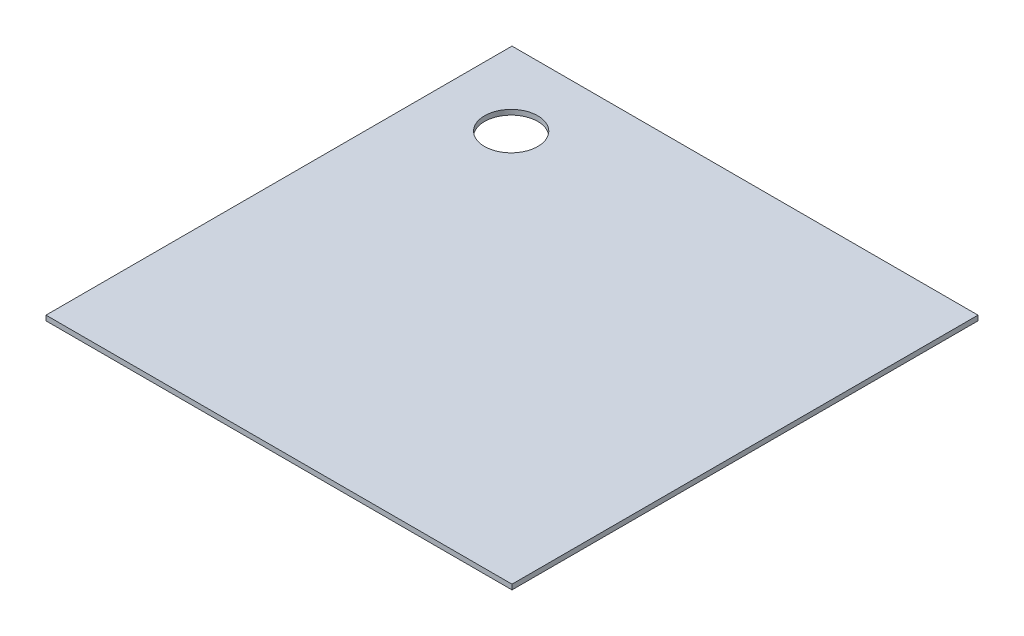
SolidWorks part; units mm, degrees
ref_plane "Front Plane" through (0, 0, 0) normal (0, 0, 1) x (1, 0, 0)
ref_plane "Top Plane" through (0, 0, 0) normal (0, 1, 0) x (1, 0, 0)
ref_plane "Right Plane" through (0, 0, 0) normal (1, 0, 0) x (0, 0, -1)
sketch "Sketch1" plane through (0, 0, 0) normal (0, 1, 0) x (1, 0, 0)
  line L1 (140, -140) -> (-140, -140)
  line L2 (140, -140) -> (140, 140)
  line L3 (140, 140) -> (-140, 140)
  line L4 (-140, -140) -> (-140, 140)
  line L5 (140, -140) -> (-140, 140) construction
  line L6 (140, 140) -> (-140, -140) construction
  circle A0 centre (-96, 95.5) radius 12.5 construction
  circle A2 centre (-96, 95.5) radius 16
  point P0 (0, 0)
  dimension "D2" = 25
  dimension "D4" = 44
  dimension "D5" = 44.5
  dimension "D3" = 32
  dimension "D1" = 280
extrude "Boss-Extrude1" add sketch "Sketch1" along normal mid plane 3
